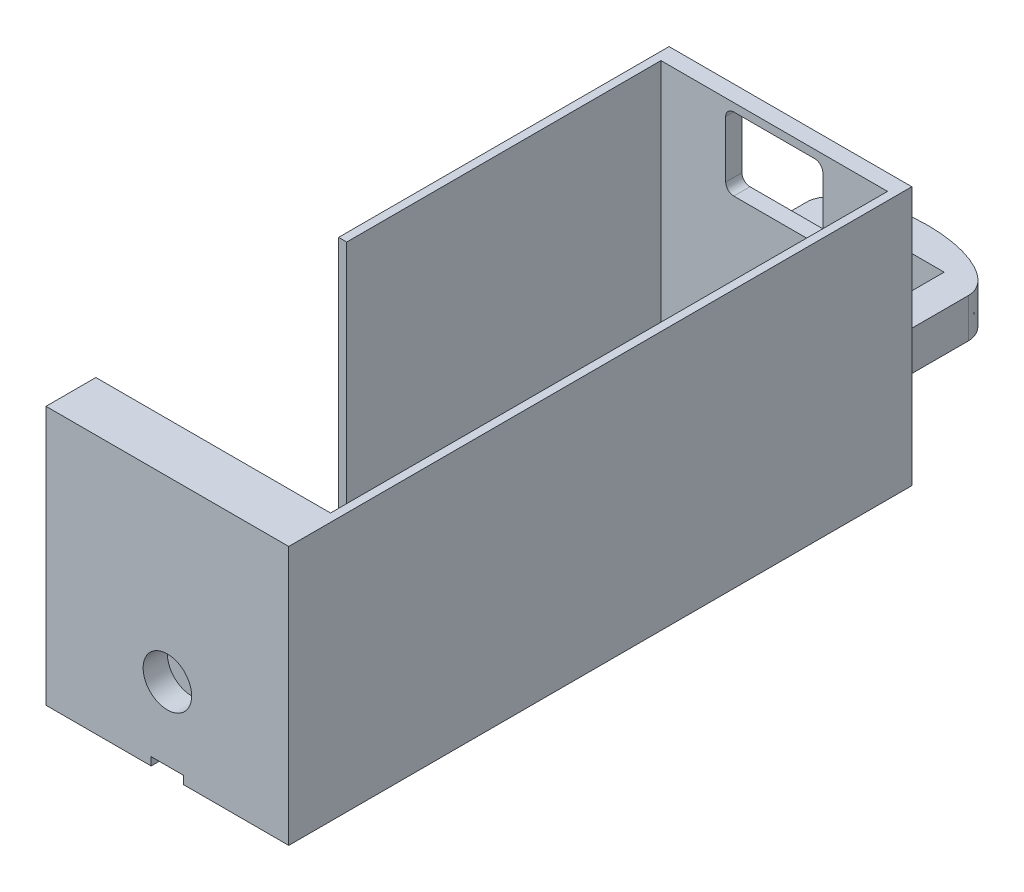
SolidWorks part; units mm, degrees
ref_plane "Plan de face" through (0, 0, 0) normal (0, 0, 1) x (1, 0, 0)
ref_plane "Plan de dessus" through (0, 0, 0) normal (0, 1, 0) x (1, 0, 0)
ref_plane "Plan de droite" through (0, 0, 0) normal (1, 0, 0) x (0, 0, -1)
sketch "Esquisse1" plane through (0, 0, 0) normal (0, 0, 1) x (1, 0, 0)
  line L1 (0, 0) -> (30, 0)
  line L2 (0, 0) -> (0, 32)
  line L3 (0, 32) -> (30, 32)
  line L4 (30, 0) -> (30, 32)
  dimension "D1" = 32
  dimension "D2" = 30
extrude "Boss.-Extru.2" add sketch "Esquisse1" along normal blind 77
sketch "Esquisse2" plane through (0, 32, 0) normal (0, 1, 0) x (1, 0, 0)
  line L0 (30, 0) -> (0, 0) construction
  line L1 (1, -2) -> (29, -2)
  line L2 (1, -2) -> (1, -70.837)
  line L3 (1, -70.837) -> (29, -70.837)
  line L4 (29, -2) -> (29, -70.837)
  line L5 (30, -77) -> (30, 0) construction
  dimension "D1" = 2
  dimension "D2" = 1
  dimension "D3" = 28
extrude "Enlèv. mat.-Extru.4" cut sketch "Esquisse2" against normal blind 30
sketch "Esquisse3" plane through (0, 0, 2) normal (0, 0, 1) x (1, 0, 0)
  line L0 (29, 2) -> (1, 2) construction
  line L1 (21, 31) -> (9, 31)
  line L2 (21, 31) -> (21, 22)
  line L3 (21, 22) -> (9, 22)
  line L4 (9, 31) -> (9, 22)
  line L10 (1, 2) -> (1, 32) construction
  dimension "D1" = 20
  dimension "D2" = 29
  dimension "D3" = 12
  dimension "D4" = 8
extrude "Enlèv. mat.-Extru.5" cut sketch "Esquisse3" against normal through all
sketch "Esquisse5" plane through (0, 0, 0) normal (0, 0, -1) x (-1, 0, 0)
  line L0 (-30, 0) -> (-30, 32) construction
  line L1 (-26, 8) -> (-6, 8)
  line L2 (-26, 8) -> (-26, 12.8563)
  line L3 (-26, 12.8563) -> (-6, 12.8563)
  line L4 (-6, 8) -> (-6, 12.8563)
  line L5 (0, 0) -> (-30, 0) construction
  dimension "D1" = 20
  dimension "D2" = 4
  dimension "D3" = 8
extrude "Boss.-Extru.3" add sketch "Esquisse5" along normal blind 16
sketch "Esquisse6" plane through (0, 12.8563, 0) normal (0, 1, 0) x (1, 0, 0)
  line L0 (6, 0) -> (26, 0) construction
  line L1 (22, 12) -> (10, 12)
  line L2 (22, 12) -> (22, 0)
  line L3 (22, 0) -> (10, 0)
  line L4 (10, 12) -> (10, 0)
  line L5 (26, 16) -> (26, 0) construction
  line L6 (6, 16) -> (6, 0) construction
  dimension "D1" = 12
  dimension "D2" = 4
  dimension "D3" = 4
extrude "Enlèv. mat.-Extru.6" cut sketch "Esquisse6" against normal blind 6
sketch "Esquisse7" plane through (0, 0, 0) normal (-1, 0, 0) x (0, 0, 1)
  line L0 (77, 32) -> (0, 32) construction
  line L1 (70.837, 32) -> (40.837, 32)
  line L2 (70.837, 32) -> (70.837, 2)
  line L3 (70.837, 2) -> (40.837, 2)
  line L4 (40.837, 32) -> (40.837, 2)
  line L5 (77, 0) -> (0, 0) construction
  dimension "D1" = 2
  dimension "D2" = 30
  dimension "D4" = 0
extrude "Enlèv. mat.-Extru.7" cut sketch "Esquisse7" against normal blind 6
fillet "Congé3" radius 5 4 edges at (6, 8, -8) (6, 12.8563, -8) (6, 10.4282, -16) (16, 12.8563, -16)
fillet "Congé5" radius 5 5 edges at (26, 12.8563, -8) (26, 8, -8) (26, 10.4282, -16)
sketch "Esquisse10" plane through (0, 0, 0) normal (0, 0, -1) x (-1, 0, 0)
  line L0 (0, 0) -> (-30, 0) construction
  line L1 (-17, 0) -> (-13, 0)
  line L2 (-17, 0) -> (-17, 1)
  line L3 (-17, 1) -> (-13, 1)
  line L4 (-13, 0) -> (-13, 1)
  dimension "D1" = 1
  dimension "D2" = 4
  dimension "D3" = 13
extrude "Enlèv. mat.-Extru.9" cut sketch "Esquisse10" against normal through all contours L3 L4 L1 L2
sketch "Esquisse16" plane through (0, 0, 77) normal (0, 0, 1) x (1, 0, 0)
  line L0 (0, 32) -> (0, 0) construction
  line L1 (0, 0) -> (13, 0) construction
  circle A0 centre (15, 10) radius 3
  dimension "D1" = 15
  dimension "D2" = 10
extrude "Enlèv. mat.-Extru.11" cut sketch "Esquisse16" against normal blind 3
sketch "Esquisse18" plane through (0, 0, 77) normal (0, 0, 1) x (1, 0, 0)
fillet "Congé7" radius 1 4 edges at (21, 31, 1) (21, 22, 1) (9, 22, 1) (9, 31, 1)
